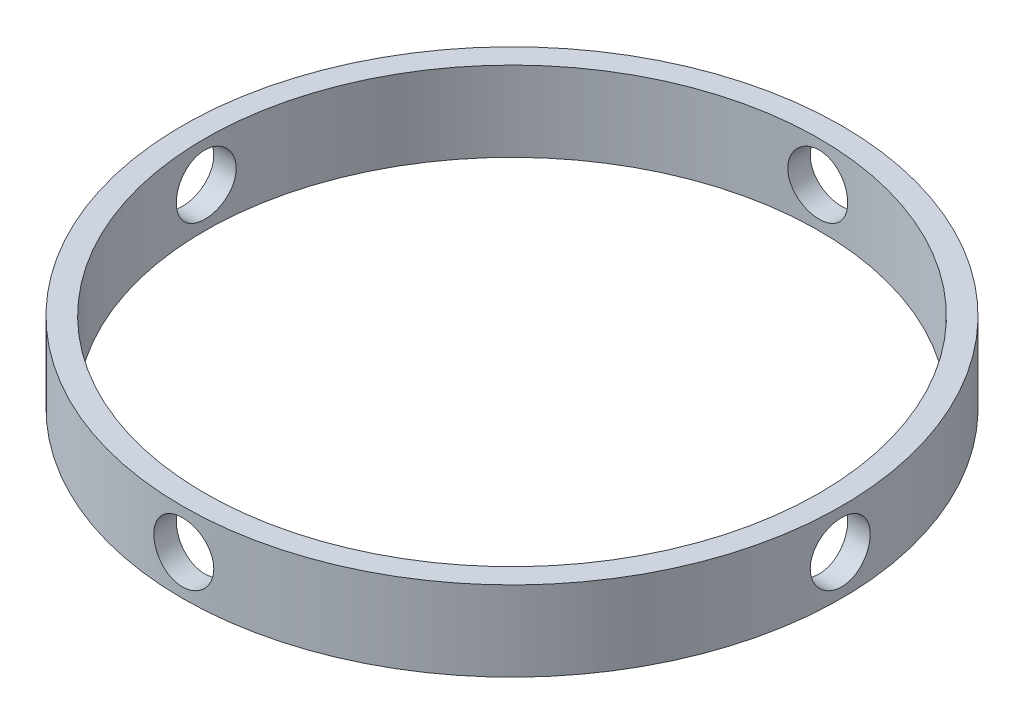
SolidWorks part; units mm, degrees
material "6061-T6 (SS)"
ref_plane "Front Plane" through (0, 0, 0) normal (0, 0, 1) x (1, 0, 0)
ref_plane "Top Plane" through (0, 0, 0) normal (0, 1, 0) x (1, 0, 0)
ref_plane "Right Plane" through (0, 0, 0) normal (1, 0, 0) x (0, 0, -1)
sketch "Sketch1" plane through (0, 0, 0) normal (0, 1, 0) x (1, 0, 0)
  circle A0 centre (0, 0) radius 82.5
  dimension "D1" = 165
extrude "Extrude-Thin1" add sketch "Sketch1" along normal blind 20 thin thin type one direction reverse wall 5.6
sketch "Sketch2" plane through (0, 0, 0) normal (1, 0, 0) x (0, 0, -1)
  line L0 (-82.5, 0) -> (82.5, 0) construction
  circle A0 centre (0, 10) radius 7.5
  dimension "D1" = 15
  dimension "D2" = 10
extrude "Cut-Extrude1" cut sketch "Sketch2" against normal blind 100 and the other way blind 100
pattern_circular "CirPattern1" count 2 every 90 about axis through (0, 20, 0) along (0, -1, 0) of "Cut-Extrude1"
